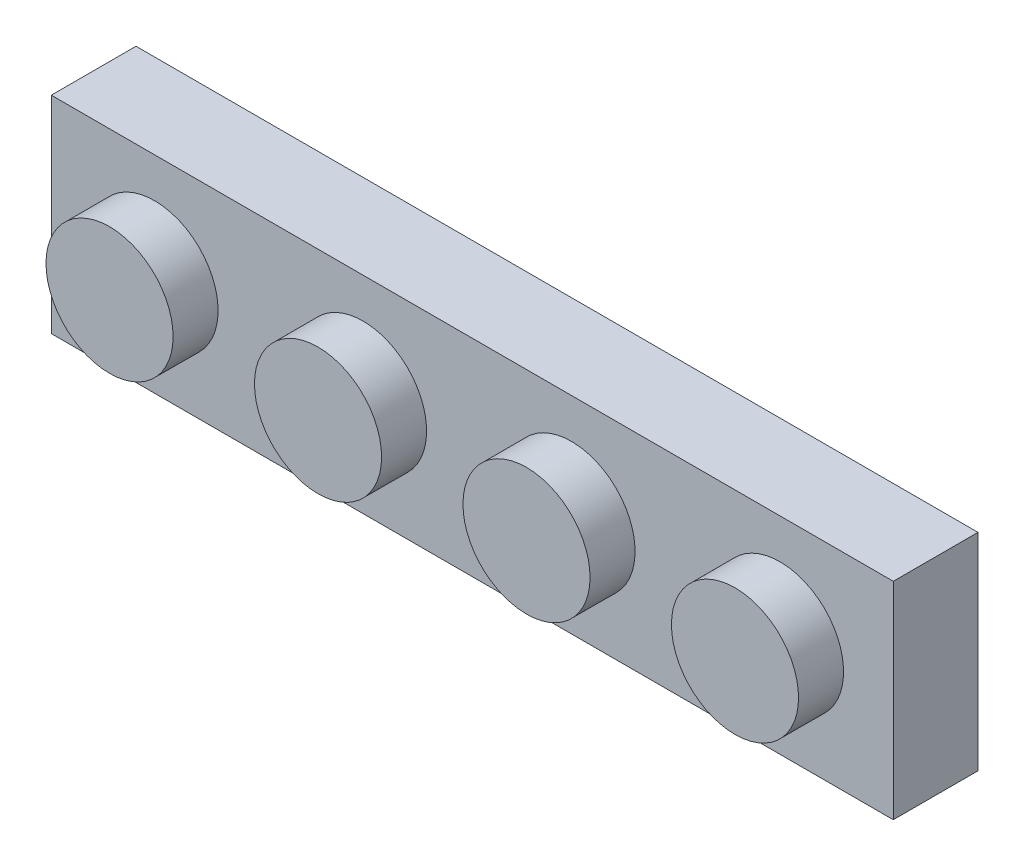
SolidWorks part; units mm, degrees
ref_plane "Спереди" through (0, 0, 0) normal (0, 0, 1) x (1, 0, 0)
ref_plane "Сверху" through (0, 0, 0) normal (0, 1, 0) x (1, 0, 0)
ref_plane "Справа" through (0, 0, 0) normal (1, 0, 0) x (0, 0, -1)
sketch "Эскиз1" plane through (0, 0, 0) normal (0, 0, 1) x (1, 0, 0)
  line L1 (15.9, -3.9) -> (-15.9, -3.9)
  line L2 (15.9, -3.9) -> (15.9, 3.9)
  line L3 (15.9, 3.9) -> (-15.9, 3.9)
  line L4 (-15.9, -3.9) -> (-15.9, 3.9)
  line L5 (15.9, -3.9) -> (-15.9, 3.9) construction
  line L6 (15.9, 3.9) -> (-15.9, -3.9) construction
  point P0 (0, 0)
  dimension "D1" = 31.8
  dimension "D2" = 7.8
extrude "Бобышка-Вытянуть1" add sketch "Эскиз1" along normal blind 3.2 contours L2 L1 L4 L3
sketch "Эскиз2" plane through (0, 0, 3.2) normal (0, 0, 1) x (1, 0, 0)
  line L0 (-15.9, -3.9) -> (-15.9, 3.9) construction
  line L1 (15.9, -3.9) -> (-15.9, -3.9) construction
  circle A0 centre (-12, 0) radius 2.4
  circle A1 centre (-4.126, 0) radius 2.4
  circle A2 centre (3.748, 0) radius 2.4
  circle A3 centre (11.622, 0) radius 2.4
  dimension "D1" = 3.9
  dimension "D2" = 3.9
  dimension "D3" = 4
extrude "Бобышка-Вытянуть2" add sketch "Эскиз2" along normal blind 1.7
sketch "Эскиз3" plane through (0, 0, 0) normal (0, 0, -1) x (-1, 0, 0)
  line L0 (-15.9, -3.9) -> (-15.9, 3.9) construction
  line L1 (-15.9, -3.9) -> (15.9, -3.9) construction
  circle A0 centre (-12, 0) radius 2.5
  circle A1 centre (-4.126, 0) radius 2.5
  circle A2 centre (3.748, 0) radius 2.5
  circle A3 centre (11.622, 0) radius 2.5
  dimension "D1" = 3.9
  dimension "D2" = 3.9
  dimension "D3" = 4
extrude "Вырез-Вытянуть1" cut sketch "Эскиз3" against normal blind 1.8
